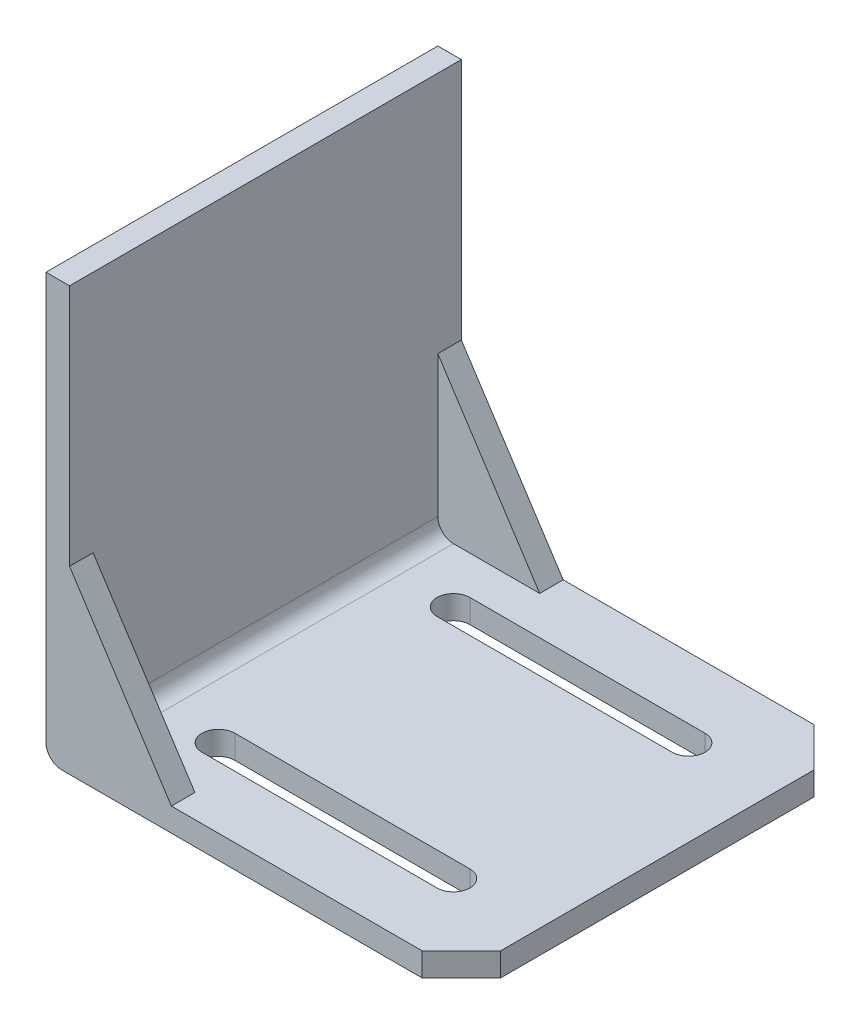
SolidWorks part; units mm, degrees
ref_plane "前视基准面" through (0, 0, 0) normal (0, 0, 1) x (1, 0, 0)
ref_plane "上视基准面" through (0, 0, 0) normal (0, 1, 0) x (1, 0, 0)
ref_plane "右视基准面" through (0, 0, 0) normal (1, 0, 0) x (0, 0, -1)
sketch "草图1" plane through (0, 0, 0) normal (0, 1, 0) x (1, 0, 0)
  line L1 (-26.5, -25) -> (26.5, -25)
  line L2 (-26.5, -25) -> (-26.5, 25)
  line L3 (-26.5, 25) -> (26.5, 25)
  line L4 (26.5, -25) -> (26.5, 25)
  line L5 (-26.5, -25) -> (26.5, 25) construction
  line L6 (-26.5, 25) -> (26.5, -25) construction
  point P0 (0, 0)
  dimension "D1" = 53
  dimension "D2" = 50
extrude "凸台-拉伸1" add sketch "草图1" along normal blind 3
chamfer "倒角1" distance 5 angle 45 2 edges at (26.5, 1.5, -25) (26.5, 1.5, 25)
sketch "草图2" plane through (0, 3, 0) normal (0, 1, 0) x (1, 0, 0)
  line L0 (-14.5, 15) -> (15.5, 15) construction
  line L1 (-14.5, 17.1) -> (15.5, 17.1)
  line L2 (-14.5, 12.9) -> (15.5, 12.9)
  line L3 (-14.5, -15) -> (15.5, -15) construction
  line L4 (-14.5, -12.9) -> (15.5, -12.9)
  line L5 (-14.5, -17.1) -> (15.5, -17.1)
  line L6 (26.5, -20) -> (26.5, 20) construction
  arc A0 (-14.5, 17.1) -> (-14.5, 12.9) centre (-14.5, 15) ccw
  arc A1 (15.5, 12.9) -> (15.5, 17.1) centre (15.5, 15) ccw
  arc A2 (-14.5, -12.9) -> (-14.5, -17.1) centre (-14.5, -15) ccw
  arc A3 (15.5, -17.1) -> (15.5, -12.9) centre (15.5, -15) ccw
  point P2 (0.5, 15)
  point P7 (0.5, -15)
  dimension "D1" = 30
  dimension "D2" = 30
  dimension "D3" = 30
  dimension "D4" = 15
  dimension "D5" = 11
  dimension "D6" = 4.2
  dimension "D7" = 4.2
extrude "切除-拉伸1" cut sketch "草图2" against normal up to next
sketch "草图3" plane through (0, 3, 0) normal (0, 1, 0) x (1, 0, 0)
  line L0 (-26.5, -25) -> (21.5, -25) construction
  line L1 (-26.5, 25) -> (-23.5, 25)
  line L2 (-26.5, 25) -> (-26.5, -25)
  line L3 (-26.5, -25) -> (-23.5, -25)
  line L4 (-23.5, 25) -> (-23.5, -25)
  dimension "D1" = 3
extrude "凸台-拉伸2" add sketch "草图3" along normal blind 51
fillet "圆角1" radius 2 2 edges at (-26.5, 0, 0) (-23.5, 3, 0)
sketch "草图6" plane through (0, 0, 25) normal (0, 0, 1) x (1, 0, 0)
  line L0 (-23.5, 23) -> (-10.5, 3)
  line L1 (-23.5, 54) -> (-23.5, 5) construction
  line L2 (-21.5, 3) -> (21.5, 3) construction
  dimension "D1" = 20
  dimension "D2" = 13
rib "筋1" sketch "草图6" sketch "草图6" thickness 3 extrusion direction parallel to sketch draft on no parameters "D1"=3
sketch "草图8" plane through (0, 0, -25) normal (0, 0, -1) x (-1, 0, 0)
  line L0 (10.5, 3) -> (23.5, 23)
  line L1 (-21.5, 3) -> (21.5, 3) construction
  line L2 (23.5, 54) -> (23.5, 5) construction
  line L3 (10.5, 3) -> (21.5, 3) construction
  line L4 (23.5, 5) -> (23.5, 23) construction
  dimension "D1" = 20
  dimension "D2" = 13
rib "筋3" sketch "草图8" sketch "草图8" thickness 3 extrusion direction parallel to sketch draft on no parameters "D1"=3
